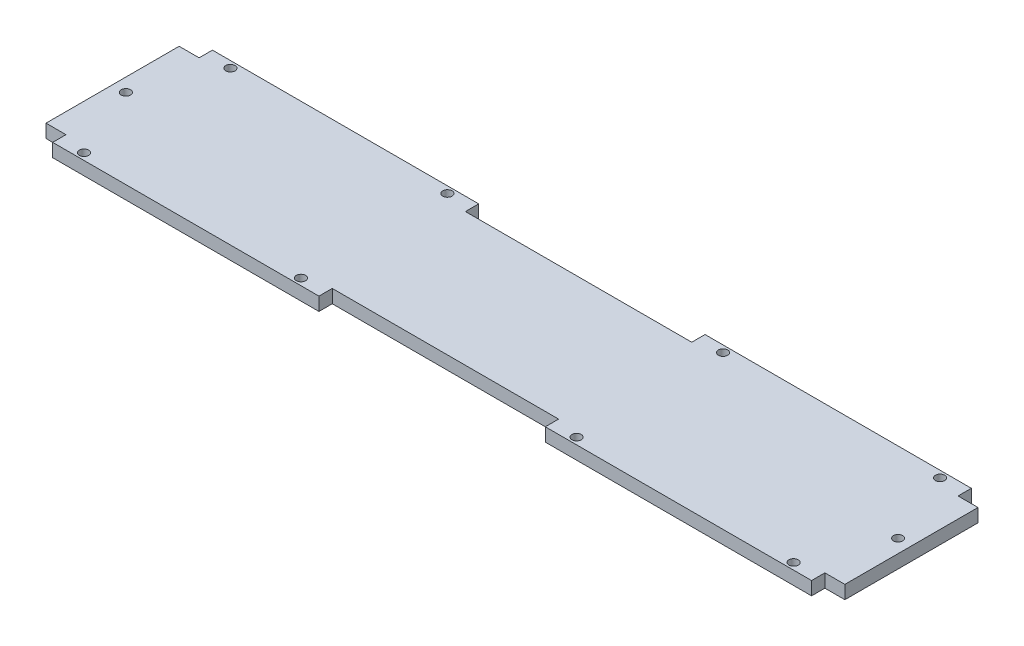
SolidWorks part; units mm, degrees
ref_plane "Front Plane" through (0, 0, 0) normal (0, 0, 1) x (1, 0, 0)
ref_plane "Top Plane" through (0, 0, 0) normal (0, 1, 0) x (1, 0, 0)
ref_plane "Right Plane" through (0, 0, 0) normal (1, 0, 0) x (0, 0, -1)
sketch "Sketch1" plane through (0, 0, 0) normal (0, 1, 0) x (1, 0, 0)
  line L0 (-92.5, -1005) -> (-92.5, 48995) construction
  line L1 (-142.5, -5) -> (-42.5, -5)
  line L2 (-142.5, -5) -> (-142.5, 0)
  line L3 (-142.5, 0) -> (-42.5, 0)
  line L4 (-42.5, -5) -> (-42.5, 0)
  line L5 (-150, 50) -> (150, 50)
  line L6 (-150, 50) -> (-150, 0)
  line L7 (-150, 0) -> (150, 0)
  line L8 (150, 50) -> (150, 0)
  line L9 (0, -1000) -> (0, 49000) construction
  line L10 (142.5, 0) -> (42.5, 0)
  line L11 (42.5, -5) -> (42.5, 0)
  line L12 (142.5, -5) -> (42.5, -5)
  line L13 (142.5, -5) -> (142.5, 0)
  line L14 (-1150, 25) -> (48850, 25) construction
  line L15 (142.5, 55) -> (142.5, 50)
  line L16 (142.5, 55) -> (42.5, 55)
  line L17 (42.5, 55) -> (42.5, 50)
  line L18 (142.5, 50) -> (42.5, 50)
  line L19 (-142.5, 50) -> (-42.5, 50)
  line L20 (-42.5, 55) -> (-42.5, 50)
  line L21 (-142.5, 55) -> (-42.5, 55)
  line L22 (-142.5, 55) -> (-142.5, 50)
  circle A0 centre (-51.75, -2.5) radius 1.75
  circle A2 centre (-133.25, -2.5) radius 1.75
  circle A3 centre (51.75, -2.5) radius 1.75
  circle A4 centre (133.25, -2.5) radius 1.75
  circle A5 centre (133.25, 52.5) radius 1.75
  circle A6 centre (51.75, 52.5) radius 1.75
  circle A7 centre (-51.75, 52.5) radius 1.75
  circle A8 centre (-133.25, 52.5) radius 1.75
  point P8 (0, 0)
  point P12 (-50, -2.5)
  point P16 (-135, -2.5)
  point P18 (-92.5, -5)
  point P20 (-42.5, -2.5)
  point P33 (-150, 25)
  dimension "D6" = 3.5
  dimension "D1" = 5
  dimension "D2" = 50
  dimension "D3" = 300
  dimension "D4" = 7.5
  dimension "D5" = 50
  dimension "D7" = 15
extrude "Boss-Extrude1" add sketch "Sketch1" along normal blind 5 contours L8 L5 L6 L7 L3 | L1 L4 L3 L2 A0 A2 | L12 L13 L7 L11 A4 A3 | L19 L20 L21 L22 | L15 L18 L17 L16 | A8 | A7 | A6 | A5 region at (-92.5, 0, 2.5) region at (0, 0, -25) region at (92.5, 0, 2.5)
sketch "Sketch2" plane through (0, 5, 0) normal (0, 1, 0) x (1, 0, 0)
  line L0 (-150, 50) -> (-150, 0) construction
  line L1 (0, -1000) -> (0, 49000) construction
  circle A0 centre (-145, 25) radius 1.75
  circle A1 centre (145, 25) radius 1.75
  point P5 (-150, 25)
  dimension "D1" = 3.5
  dimension "D2" = 5
extrude "Cut-Extrude1" cut sketch "Sketch2" against normal blind 10
